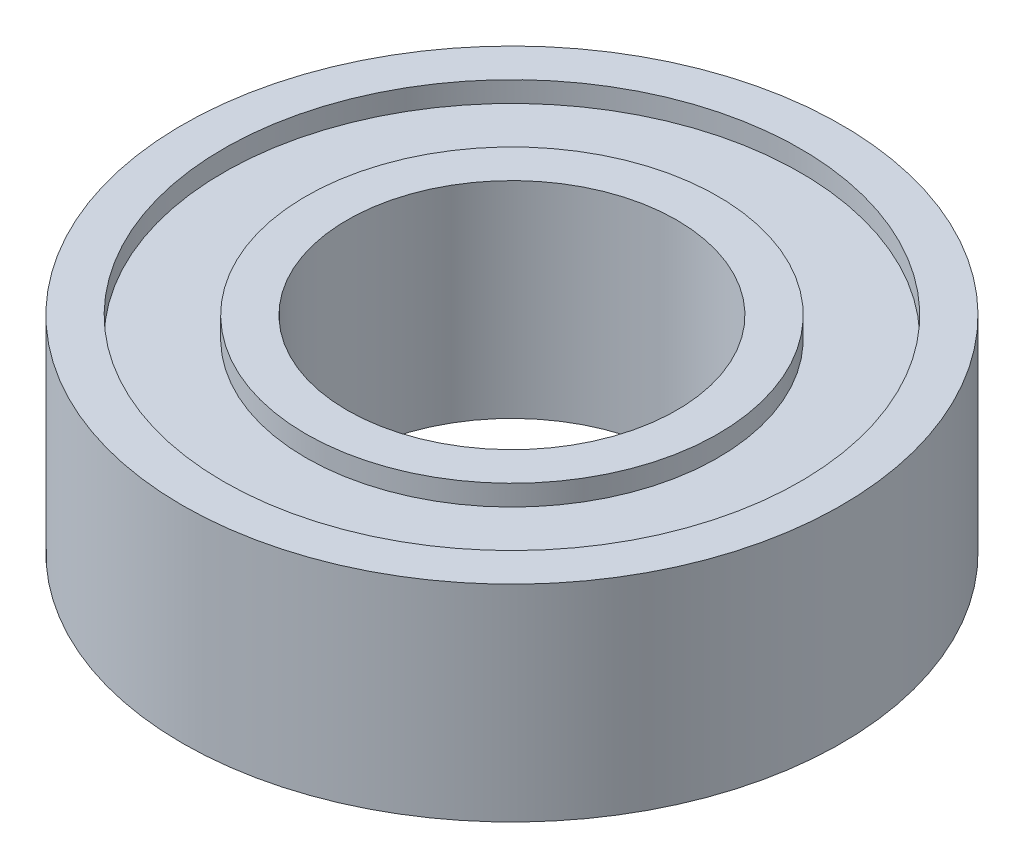
SolidWorks part; units mm, degrees
ref_plane "Front Plane" through (0, 0, 0) normal (0, 0, 1) x (1, 0, 0)
ref_plane "Top Plane" through (0, 0, 0) normal (0, 1, 0) x (1, 0, 0)
ref_plane "Right Plane" through (0, 0, 0) normal (1, 0, 0) x (0, 0, -1)
sketch "Sketch2" plane through (0, 0, 0) normal (0, 1, 0) x (1, 0, 0)
  circle A0 centre (0, 0) radius 8
  circle A1 centre (0, 0) radius 4
  circle A2 centre (0, 0) radius 5
  circle A3 centre (0, 0) radius 7
  dimension "D1" = 16
  dimension "D2" = 8
  dimension "D3" = 10
  dimension "D4" = 14
extrude "Boss-Extrude1" add sketch "Sketch2" along normal blind 5 contours A0 A3 | A2 A1 region at (-7.7737, 0, 0) region at (-4.8586, 0, 0)
extrude "Boss-Extrude2" add sketch "Sketch2<3>" along normal blind 4 from offset 0.5 contours A3 A2 region at (-6.802, 0, 0)
sketch "Sketch2<3>" plane through (0, 0, 0) normal (0, 1, 0) x (1, 0, 0) same geometry as "Sketch2"
